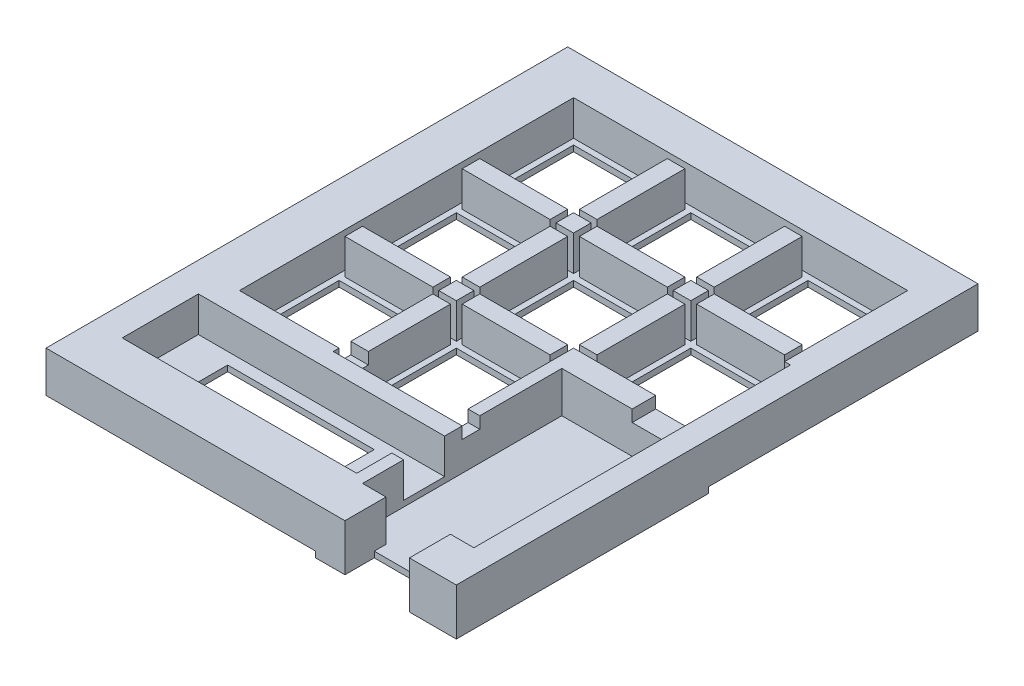
SolidWorks part; units mm, degrees
ref_plane "前视基准面" through (0, 0, 0) normal (0, 0, 1) x (1, 0, 0)
ref_plane "上视基准面" through (0, 0, 0) normal (0, 1, 0) x (1, 0, 0)
ref_plane "右视基准面" through (0, 0, 0) normal (1, 0, 0) x (0, 0, -1)
sketch "草图1" plane through (0, 0, 0) normal (0, 1, 0) x (1, 0, 0)
  line L1 (0, 0) -> (71, 0)
  line L2 (0, 0) -> (0, 67)
  line L3 (0, 67) -> (71, 67)
  line L4 (71, 0) -> (71, 67)
  dimension "D1" = 71
  dimension "D2" = 67
extrude "凸台-拉伸2" add sketch "草图1" along normal blind 5
extrude "凸台-拉伸3" add sketch "草图1<2>" along normal blind 7
sketch "草图1<2>" plane through (0, 0, 0) normal (0, 1, 0) x (1, 0, 0) same geometry as "草图1"
sketch "草图6" plane through (0, 0, 0) normal (0, 1, 0) x (1, 0, 0)
sketch "草图9" plane through (0, 0, 0) normal (0, 1, 0) x (1, 0, 0)
  line L0 (0, 0) -> (71, 0) construction
  line L1 (71, 0) -> (71, 67) construction
  line L3 (51, 0) -> (71, 0)
  line L4 (51, 0) -> (51, 20)
  line L5 (51, 20) -> (71, 20)
  line L6 (71, 0) -> (71, 20)
  point P0 (51, 0)
  point P1 (71, 20)
  dimension "D1" = 20
  dimension "D2" = 20
extrude "切除-拉伸5" cut sketch "草图9" along normal blind 36
sketch "草图10" plane through (0, 0, 0) normal (0, 1, 0) x (1, 0, 0)
  line L0 (71, 20) -> (71, 67) construction
  line L1 (0, 67) -> (0, 0) construction
  line L2 (71, 67) -> (0, 67) construction
  line L3 (10, 60) -> (10, 45)
  line L4 (10, 45) -> (25, 45)
  line L5 (25, 45) -> (25, 60)
  line L6 (25, 60) -> (10, 60)
  line L7 (30, 45) -> (30, 60)
  line L8 (30, 60) -> (45, 60)
  line L9 (45, 60) -> (45, 45)
  line L10 (45, 45) -> (30, 45)
  line L11 (50, 45) -> (50, 60)
  line L12 (50, 60) -> (65, 60)
  line L13 (65, 60) -> (65, 45)
  line L14 (65, 45) -> (50, 45)
  line L15 (50, 25) -> (50, 40)
  line L16 (50, 40) -> (65, 40)
  line L17 (65, 40) -> (65, 25)
  line L18 (65, 25) -> (50, 25)
  line L19 (0, 0) -> (51, 0) construction
  line L20 (30, 25) -> (45, 25)
  line L21 (30, 25) -> (30, 40)
  line L22 (30, 40) -> (45, 40)
  line L23 (45, 25) -> (45, 40)
  line L24 (10, 25) -> (25, 25)
  line L25 (10, 25) -> (10, 40)
  line L26 (10, 40) -> (25, 40)
  line L27 (25, 25) -> (25, 40)
  line L28 (10, 5) -> (25, 5)
  line L29 (10, 5) -> (10, 20)
  line L30 (10, 20) -> (25, 20)
  line L31 (25, 5) -> (25, 20)
  line L32 (30, 5) -> (45, 5)
  line L33 (30, 5) -> (30, 20)
  line L34 (30, 20) -> (45, 20)
  line L35 (45, 5) -> (45, 20)
  line L36 (50, 0) -> (51, 0)
  line L37 (50, 0) -> (50, 20)
  line L38 (50, 20) -> (51, 20)
  line L39 (51, 0) -> (51, 20)
  line L40 (51, 20) -> (51, 0) construction
  point P0 (71, 60)
  point P1 (71, 45)
  point P5 (71, 40)
  point P6 (71, 25)
  point P7 (0, 5)
  point P8 (0, 0)
  point P11 (0, 5)
  point P13 (0, 20)
  point P14 (0, 20)
  point P15 (0, 5)
  point P16 (65, 67)
  point P17 (50, 67)
  point P20 (45, 67)
  point P21 (30, 67)
  point P22 (25, 67)
  point P23 (10, 67)
  point P64 (66, 67)
  point P65 (49, 67)
  point P66 (45.5452, 67)
  dimension "D1" = 7
  dimension "D2" = 15
  dimension "D3" = 5
  dimension "D4" = 15
  dimension "D5" = 5
  dimension "D6" = 15
  dimension "D7" = 6
  dimension "D8" = 15
  dimension "D9" = 5
  dimension "D10" = 15
  dimension "D11" = 5
  dimension "D12" = 15
  dimension "D13" = 1
  dimension "D14" = 1
extrude "切除-拉伸6" cut sketch "草图10" along normal blind 32
ref_plane "上中" through (0, 1, 0) normal (0, 1, 0) x (1, 0, 0)
sketch "草图14" plane through (0, 1, 0) normal (0, 1, 0) x (1, 0, 0)
  line L0 (0, 67) -> (0, 0) construction
  line L5 (71, 67) -> (0, 67) construction
  line L6 (71, 20) -> (71, 67) construction
  line L7 (66, 24) -> (65, 24)
  line L12 (50, 61) -> (49, 61)
  line L13 (50, 61) -> (50, 24)
  line L14 (50, 24) -> (49, 24)
  line L15 (49, 61) -> (49, 24)
  line L16 (66, 24) -> (66, 61)
  line L17 (66, 61) -> (65, 61)
  line L18 (65, 24) -> (65, 61)
  line L32 (30, 61) -> (29, 61)
  line L33 (30, 61) -> (30, 4)
  line L34 (30, 4) -> (29, 4)
  line L35 (29, 61) -> (29, 4)
  line L36 (25, 4) -> (26, 4)
  line L37 (25, 4) -> (25, 61)
  line L38 (25, 61) -> (26, 61)
  line L39 (26, 4) -> (26, 61)
  line L40 (9, 4) -> (10, 4)
  line L41 (9, 4) -> (9, 61)
  line L42 (9, 61) -> (10, 61)
  line L43 (10, 4) -> (10, 61)
  line L44 (46, 4) -> (45, 4)
  line L45 (46, 4) -> (46, 61)
  line L46 (46, 61) -> (45, 61)
  line L47 (45, 4) -> (45, 61)
  point P0 (66, 67)
  point P1 (65, 67)
  point P4 (71, 24)
  point P5 (71, 61)
  point P12 (50, 67)
  point P15 (49, 67)
  point P16 (46, 67)
  point P21 (45, 67)
  point P26 (30, 67)
  point P27 (29, 67)
  point P28 (26, 67)
  point P29 (25, 67)
  point P34 (10, 67)
  point P35 (9, 67)
  point P40 (0, 5)
  point P41 (0, 4)
  dimension "D1" = 5
  dimension "D2" = 1
  dimension "D3" = 4
  dimension "D4" = 6
  dimension "D5" = 21
  dimension "D6" = 1
  dimension "D7" = 3
  dimension "D8" = 1
  dimension "D9" = 15
  dimension "D10" = 1
  dimension "D11" = 3
  dimension "D12" = 1
  dimension "D13" = 15
  dimension "D14" = 1
  dimension "D15" = 5
  dimension "D16" = 1
extrude "切除-拉伸7" cut sketch "草图14" along normal blind 19
sketch "草图15" plane through (0, 1, 0) normal (0, 1, 0) x (1, 0, 0)
  line L0 (0, 67) -> (0, 0) construction
  line L1 (71, 67) -> (0, 67) construction
  line L3 (9, 4) -> (46, 4)
  line L4 (9, 4) -> (9, 5)
  line L5 (9, 5) -> (46, 5)
  line L6 (46, 4) -> (46, 5)
  line L7 (9, 25) -> (66, 25)
  line L8 (9, 25) -> (9, 24)
  line L9 (9, 24) -> (66, 24)
  line L10 (66, 25) -> (66, 24)
  line L11 (9, 45) -> (66, 45)
  line L12 (9, 45) -> (9, 44)
  line L13 (9, 44) -> (66, 44)
  line L14 (66, 45) -> (66, 44)
  line L15 (9, 20) -> (46, 20)
  line L16 (9, 20) -> (9, 21)
  line L17 (9, 21) -> (46, 21)
  line L18 (46, 20) -> (46, 21)
  line L19 (9, 40) -> (66, 40)
  line L20 (9, 40) -> (9, 41)
  line L21 (9, 41) -> (66, 41)
  line L22 (66, 40) -> (66, 41)
  line L23 (9, 60) -> (66, 60)
  line L24 (9, 60) -> (9, 61)
  line L25 (9, 61) -> (66, 61)
  line L26 (66, 60) -> (66, 61)
  point P0 (0, 4)
  point P1 (0, 5)
  point P5 (0, 20)
  point P6 (0, 21)
  point P7 (0, 24)
  point P8 (0, 25)
  point P9 (0, 40)
  point P10 (0, 41)
  point P11 (0, 44)
  point P12 (0, 45)
  point P13 (0, 60)
  point P14 (0, 61)
  point P15 (66, 67)
  point P16 (49, 67)
  point P20 (9, 67)
  point P21 (46, 67)
  dimension "D1" = 4
  dimension "D2" = 1
  dimension "D3" = 15
  dimension "D4" = 1
  dimension "D5" = 3
  dimension "D6" = 1
  dimension "D7" = 15
  dimension "D8" = 1
  dimension "D9" = 3
  dimension "D10" = 1
  dimension "D11" = 15
  dimension "D12" = 1
  dimension "D13" = 5
  dimension "D14" = 22
  dimension "D15" = 62
  dimension "D16" = 25
extrude "切除-拉伸8" cut sketch "草图15" along normal blind 27
sketch "草图16" plane through (0, 0, 0) normal (0, 1, 0) x (1, 0, 0)
  line L0 (0, 0) -> (50, 0) construction
  line L1 (71, 20) -> (71, 67) construction
  line L3 (48, 0) -> (71, 0)
  line L4 (48, 0) -> (48, 21)
  line L5 (48, 21) -> (71, 21)
  line L6 (71, 0) -> (71, 21)
  point P0 (48, 0)
  point P1 (71, 21)
  dimension "D1" = 2
  dimension "D2" = 1
extrude "切除-拉伸9" cut sketch "草图16" along normal blind 17
sketch "草图17" plane through (0, 0, 0) normal (0, 1, 0) x (1, 0, 0)
  line L0 (71, 67) -> (0, 67) construction
  line L2 (1, 67) -> (0, 67)
  line L3 (1, 67) -> (1, 0)
  line L4 (1, 0) -> (0, 0)
  line L5 (0, 67) -> (0, 0)
  point P0 (1, 67)
  point P1 (1, 67)
  point P4 (0, 67)
  dimension "D1" = 1
extrude "切除-拉伸10" cut sketch "草图17" along normal blind 27
ref_plane "上下" through (0, 7, 0) normal (0, 1, 0) x (1, 0, 0)
sketch "草图18" plane through (0, 7, 0) normal (0, 1, 0) x (1, 0, 0)
  line L0 (66, 24) -> (66, 61) construction
  line L1 (66, 40) -> (67, 40)
  line L2 (66, 40) -> (66, 21)
  line L3 (66, 21) -> (67, 21)
  line L4 (67, 40) -> (67, 21)
  line L5 (71, 21) -> (48, 21) construction
extrude "切除-拉伸11" cut sketch "草图18" against normal blind 1
sketch "草图19" plane through (0, 7, 0) normal (0, 1, 0) x (1, 0, 0)
  line L1 (65, 40) -> (67, 40)
  line L2 (65, 40) -> (65, 21)
  line L3 (65, 21) -> (67, 21)
  line L4 (67, 40) -> (67, 21)
extrude "切除-拉伸12" cut sketch "草图19" against normal blind 1
sketch "草图20" plane through (0, 7, 0) normal (0, 1, 0) x (1, 0, 0)
  line L0 (65, 21) -> (48, 21) construction
  line L1 (46, 24) -> (66, 24) construction
  line L2 (63, 21) -> (64, 21)
  line L3 (63, 21) -> (63, 24)
  line L4 (63, 24) -> (64, 24)
  line L5 (64, 21) -> (64, 24)
  point P0 (64, 21)
  point P1 (63, 21)
  dimension "D1" = 1
  dimension "D2" = 1
extrude "切除-拉伸13" cut sketch "草图20" against normal blind 1
sketch "草图21" plane through (0, 7, 0) normal (0, 1, 0) x (1, 0, 0)
  line L0 (46, 4) -> (46, 24) construction
  line L1 (48, 21) -> (48, 0) construction
  line L2 (46, 5) -> (48, 5)
  line L3 (46, 5) -> (46, 6)
  line L4 (46, 6) -> (48, 6)
  line L5 (48, 5) -> (48, 6)
  point P0 (46, 6)
  dimension "D1" = 2
extrude "切除-拉伸15" cut sketch "草图21" against normal blind 1
sketch "草图22" plane through (0, 7, 0) normal (0, 1, 0) x (1, 0, 0)
  line L0 (48, 21) -> (48, 6) construction
  line L2 (48, 20) -> (71, 20)
  line L3 (48, 20) -> (48, 21)
  line L4 (48, 21) -> (71, 21)
  line L5 (71, 20) -> (71, 21)
  point P0 (48, 20)
  dimension "D1" = 1
extrude "凸台-拉伸4" add sketch "草图22" against normal up to vertex (7 mm away) up to point (48, 0, -21)
sketch "草图23" plane through (0, 7, 0) normal (0, 1, 0) x (1, 0, 0)
  line L0 (48, 20) -> (71, 20) construction
  line L1 (63, 21) -> (64, 21)
  line L2 (63, 21) -> (63, 20)
  line L3 (63, 20) -> (64, 20)
  line L4 (64, 21) -> (64, 20)
  line L6 (65, 21) -> (67, 21)
  line L7 (65, 21) -> (65, 20)
  line L8 (65, 20) -> (67, 20)
  line L9 (67, 21) -> (67, 20)
extrude "切除-拉伸16" cut sketch "草图23" against normal blind 1
sketch "草图24" plane through (0, 7, 0) normal (0, 1, 0) x (1, 0, 0)
  line L1 (1, 67) -> (71, 67)
  line L2 (1, 67) -> (1, 68)
  line L3 (1, 68) -> (71, 68)
  line L4 (71, 67) -> (71, 68)
extrude "凸台-拉伸5" add sketch "草图24" against normal blind 7
sketch "草图27" plane through (0, 7, 0) normal (0, 1, 0) x (1, 0, 0)
  line L0 (1, 0) -> (48, 0) construction
  line L2 (6, 0) -> (1, 0)
  line L3 (6, 0) -> (6, -20)
  line L4 (6, -20) -> (1, -20)
  line L5 (1, 0) -> (1, -20)
  point P0 (6, 0)
  dimension "D1" = 5
extrude "凸台-拉伸6" add sketch "草图27" against normal blind 7
sketch "草图28" plane through (0, 7, 0) normal (0, 1, 0) x (1, 0, 0)
  line L0 (6, -20) -> (6, 0) construction
  line L2 (6, -20) -> (48, -20)
  line L3 (6, -20) -> (6, -12)
  line L4 (6, -12) -> (48, -12)
  line L5 (48, -20) -> (48, -12)
  point P0 (6, -12)
  dimension "D1" = 8
extrude "凸台-拉伸7" add sketch "草图28" against normal up to vertex (7 mm away) up to point (1, 0, -68)
sketch "草图29" plane through (0, 7, 0) normal (0, 1, 0) x (1, 0, 0)
  line L0 (48, -20) -> (48, -12) construction
  line L2 (48, -13) -> (6, -13)
  line L3 (48, -13) -> (48, -12)
  line L4 (48, -12) -> (6, -12)
  line L5 (6, -13) -> (6, -12)
  point P0 (48, -13)
  dimension "D1" = 1
extrude "切除-拉伸17" cut sketch "草图29" against normal blind 7
sketch "草图30" plane through (0, 7, 0) normal (0, 1, 0) x (1, 0, 0)
  line L1 (1, -20) -> (48, -20)
  line L2 (1, -20) -> (1, -21)
  line L3 (1, -21) -> (48, -21)
  line L4 (48, -20) -> (48, -21)
extrude "凸台-拉伸8" add sketch "草图30" against normal blind 7
sketch "草图31" plane through (0, 7, 0) normal (0, 1, 0) x (1, 0, 0)
  line L0 (6, -13) -> (48, -13) construction
  line L2 (48, -13) -> (46, -13)
  line L3 (48, -13) -> (48, -10)
  line L4 (48, -10) -> (46, -10)
  line L5 (46, -13) -> (46, -10)
  point P0 (46, -13)
  dimension "D1" = 2
extrude "凸台-拉伸9" add sketch "草图31" against normal blind 7
sketch "草图32" plane through (0, 7, 0) normal (0, 1, 0) x (1, 0, 0)
  line L1 (71, 20) -> (67, 20)
  line L2 (71, 20) -> (71, -21)
  line L3 (71, -21) -> (67, -21)
  line L4 (67, 20) -> (67, -21)
extrude "凸台-拉伸11" add sketch "草图32" against normal blind 7
sketch "草图33" plane through (0, 7, 0) normal (0, 1, 0) x (1, 0, 0)
  line L0 (67, -21) -> (67, 40) construction
  line L2 (67, -21) -> (63, -21)
  line L3 (67, -21) -> (67, -17)
  line L4 (67, -17) -> (63, -17)
  line L5 (63, -21) -> (63, -17)
  point P0 (67, -17)
  dimension "D1" = 4
extrude "凸台-拉伸12" add sketch "草图33" against normal blind 7
sketch "草图34" plane through (0, 7, 0) normal (0, 1, 0) x (1, 0, 0)
  line L0 (48, -21) -> (48, -10) construction
  line L2 (48, -17) -> (52, -17)
  line L3 (48, -17) -> (48, -21)
  line L4 (48, -21) -> (52, -21)
  line L5 (52, -17) -> (52, -21)
  point P0 (48, -17)
  dimension "D1" = 4
extrude "凸台-拉伸13" add sketch "草图34" against normal blind 7
sketch "草图35" plane through (0, 7, 0) normal (0, 1, 0) x (1, 0, 0)
  line L0 (52, -21) -> (52, -17) construction
  line L3 (67, 20) -> (67, -17) construction
  line L4 (48, -17) -> (48, -10) construction
  line L5 (67, -17) -> (48, -17)
  line L6 (67, -17) -> (67, -14)
  line L7 (67, -14) -> (48, -14)
  line L8 (48, -17) -> (48, -14)
  point P0 (52, -19)
  point P6 (67, -14)
  dimension "D1" = 3
extrude "凸台-拉伸14" add sketch "草图35" against normal blind 7
sketch "草图36" plane through (0, 0, 0) normal (0, 1, 0) x (1, 0, 0)
  line L0 (67, -14) -> (48, -14) construction
  line L1 (52, -17) -> (63, -17)
  line L2 (52, -17) -> (52, -14)
  line L3 (52, -14) -> (63, -14)
  line L4 (63, -17) -> (63, -14)
extrude "切除-拉伸20" cut sketch "草图36" along normal blind 7
sketch "草图37" plane through (0, 7, 0) normal (0, 1, 0) x (1, 0, 0)
  line L0 (1, -21) -> (52, -21) construction
  line L1 (1, -21) -> (1, 68) construction
  line L2 (63, -21) -> (71, -21) construction
  line L3 (71, -21) -> (71, 68) construction
  line L4 (71, 68) -> (1, 68) construction
  circle A0 centre (3, -18) radius 0.5
  circle A1 centre (69.5, -18) radius 0.5
  circle A2 centre (69.5, 64) radius 0.5
  circle A3 centre (3.5, 64) radius 0.5
  point P0 (3, -21)
  point P1 (1, -18)
  point P9 (69.5, -21)
  point P10 (71, -18)
  point P18 (69.5, 68)
  point P19 (71, 64)
  point P25 (3.5, 68)
  point P26 (1, 64)
  dimension "D3" = 1.5
  dimension "D5" = 1.5
  dimension "D7" = 2.5
  dimension "D1" = 2
  dimension "D2" = 3
  dimension "D4" = 3
  dimension "D6" = 4
  dimension "D8" = 4
extrude "切除-拉伸22" cut sketch "草图37" against normal blind 9
sketch "草图38" plane through (0, 0, 0) normal (0, 1, 0) x (1, 0, 0)
  circle A0 centre (69.5, -18) radius 1
  circle A1 centre (69.5, 64) radius 1
  circle A2 centre (3.5, 64) radius 1
  circle A3 centre (3, -18) radius 1
extrude "切除-拉伸23" cut sketch "草图38" along normal blind 5
sketch "草图39" plane through (0, 7, 0) normal (0, 1, 0) x (1, 0, 0)
  line L0 (1, 68) -> (71, 68)
  line L1 (71, 68) -> (71, -21)
  line L2 (71, -21) -> (63, -21)
  line L3 (63, -21) -> (63, -14)
  line L4 (63, -14) -> (67, -14)
  line L5 (67, -14) -> (67, 40)
  line L6 (67, 40) -> (66, 40)
  line L7 (66, 40) -> (66, 61)
  line L8 (66, 61) -> (9, 61)
  line L9 (9, 61) -> (9, 4)
  line L10 (9, 4) -> (46, 4)
  line L11 (46, 4) -> (46, 5)
  line L12 (46, 5) -> (48, 5)
  line L13 (48, 5) -> (48, 0)
  line L14 (48, 0) -> (6, 0)
  line L15 (6, 0) -> (6, -13)
  line L16 (6, -13) -> (46, -13)
  line L17 (46, -13) -> (46, -10)
  line L18 (46, -10) -> (48, -10)
  line L19 (48, -10) -> (48, -14)
  line L20 (48, -14) -> (52, -14)
  line L21 (52, -14) -> (52, -21)
  line L22 (52, -21) -> (1, -21)
  line L23 (1, -21) -> (1, 68)
extrude "凸台-拉伸15" add sketch "草图39" along normal blind 1
extrude "切除-拉伸26" cut sketch "草图37<3>" against normal blind 12 and the other way blind 12
sketch "草图37<3>" plane through (0, 7, 0) normal (0, 1, 0) x (1, 0, 0) same geometry as "草图37"
sketch "草图40" plane through (0, 7, 0) normal (0, 1, 0) x (1, 0, 0)
  line L0 (46, 4) -> (46, 24) construction
  line L1 (46, 5) -> (48, 5)
  line L2 (46, 5) -> (46, 4)
  line L3 (46, 4) -> (48, 4)
  line L4 (48, 5) -> (48, 4)
  line L5 (46, 5) -> (46, 4) construction
  line L6 (48, 0) -> (48, 5) construction
extrude "切除-拉伸28" cut sketch "草图40" against normal blind 1 and the other way blind 9
sketch "草图42" plane through (0, 7, 0) normal (0, 1, 0) x (1, 0, 0)
  line L1 (48, 20) -> (63, 20) construction
  line L2 (65, 24) -> (62, 24) construction
  line L3 (65, 24) -> (65, 20) construction
  line L4 (65, 20) -> (62, 20) construction
  line L5 (62, 24) -> (62, 20) construction
  line L7 (62, 24) -> (65, 24)
  line L8 (62, 24) -> (62, 20)
  line L9 (62, 20) -> (65, 20)
  line L10 (65, 24) -> (65, 20)
extrude "切除-拉伸29" cut sketch "草图42" against normal blind 1
sketch "草图43" plane through (0, 7, 0) normal (0, 1, 0) x (1, 0, 0)
  line L0 (46, 6) -> (46, 24)
  line L1 (46, 24) -> (62, 24)
  line L2 (62, 24) -> (62, 20)
  line L3 (62, 20) -> (48, 20)
  line L4 (48, 20) -> (48, 6)
  line L5 (48, 6) -> (46, 6)
  line L6 (45, 44) -> (45, 41) construction
  line L7 (46, 40) -> (49, 40)
  line L8 (46, 40) -> (46, 25)
  line L9 (46, 25) -> (49, 25)
  line L10 (49, 40) -> (49, 25)
  line L11 (46, 60) -> (49, 60)
  line L12 (46, 60) -> (46, 45)
  line L13 (46, 45) -> (49, 45)
  line L14 (49, 60) -> (49, 45)
  line L15 (50, 44) -> (65, 44)
  line L16 (50, 44) -> (50, 41)
  line L17 (50, 41) -> (65, 41)
  line L18 (65, 44) -> (65, 41)
  line L19 (26, 60) -> (29, 60)
  line L20 (26, 60) -> (26, 45)
  line L21 (26, 45) -> (29, 45)
  line L22 (29, 60) -> (29, 45)
  line L23 (26, 40) -> (29, 40)
  line L24 (26, 40) -> (26, 25)
  line L25 (26, 25) -> (29, 25)
  line L26 (29, 40) -> (29, 25)
  line L27 (10, 44) -> (25, 44)
  line L28 (10, 44) -> (10, 41)
  line L29 (10, 41) -> (25, 41)
  line L30 (25, 44) -> (25, 41)
  line L31 (30, 44) -> (45, 44)
  line L32 (30, 44) -> (30, 41)
  line L33 (30, 41) -> (45, 41)
  line L34 (45, 44) -> (45, 41)
  line L35 (45, 41) -> (30, 41) construction
  line L37 (10, 24) -> (25, 24)
  line L38 (10, 24) -> (10, 21)
  line L39 (10, 21) -> (25, 21)
  line L40 (25, 24) -> (25, 21)
  line L41 (26, 20) -> (29, 20)
  line L42 (26, 20) -> (26, 5)
  line L43 (26, 5) -> (29, 5)
  line L44 (29, 20) -> (29, 5)
  line L45 (26, 24) -> (29, 24)
  line L46 (26, 24) -> (26, 21)
  line L47 (26, 21) -> (29, 21)
  line L48 (29, 24) -> (29, 21)
  line L49 (46, 44) -> (49, 44)
  line L50 (46, 44) -> (46, 41)
  line L51 (46, 41) -> (49, 41)
  line L52 (49, 44) -> (49, 41)
  line L53 (26, 44) -> (29, 44)
  line L54 (26, 44) -> (26, 41)
  line L55 (26, 41) -> (29, 41)
  line L56 (29, 44) -> (29, 41)
extrude "凸台-拉伸17" add sketch "草图43" along normal blind 1
sketch "草图44" plane through (0, 0, 0) normal (0, 1, 0) x (1, 0, 0)
  line L1 (46, -10) -> (48, -10)
  line L2 (46, -10) -> (46, -6.9982)
  line L3 (46, -6.9982) -> (48, -6.9982)
  line L4 (48, -10) -> (48, -6.9982)
extrude "凸台-拉伸18" add sketch "草图44" along normal blind 8
sketch "草图45" plane through (0, 1, 0) normal (0, 1, 0) x (1, 0, 0)
  line L0 (6, -13) -> (46, -13) construction
  line L1 (6, 0) -> (13, 0) construction
  line L2 (6, 0) -> (6, -13) construction
  line L3 (6, -13) -> (13, -13) construction
  line L4 (13, 0) -> (13, -13) construction
  line L6 (13, 0) -> (6, 0)
  line L7 (13, 0) -> (13, -13)
  line L8 (13, -13) -> (6, -13)
  line L9 (6, 0) -> (6, -13)
extrude "凸台-拉伸19" add sketch "草图45" along normal blind 1
sketch "草图46" plane through (0, 1, 0) normal (0, 1, 0) x (1, 0, 0)
  line L0 (6, -13) -> (46, -13) construction
  line L1 (48, 20) -> (48, 0) construction
  line L2 (38, -13) -> (48, -13)
  line L3 (38, -13) -> (38, 0)
  line L4 (38, 0) -> (48, 0)
  line L5 (48, -13) -> (48, 0)
  line L6 (6, 0) -> (48, 0) construction
  point P0 (38, -13)
  dimension "D1" = 32
extrude "凸台-拉伸20" add sketch "草图46" along normal blind 1
sketch "草图49" plane through (0, 0, 0) normal (0, 1, 0) x (1, 0, 0)
  line L1 (46, -14) -> (68.3792, -14)
  line L2 (46, -14) -> (46, 20.513)
  line L3 (46, 20.513) -> (68.3792, 20.513)
  line L4 (68.3792, -14) -> (68.3792, 20.513)
extrude "凸台-拉伸26" add sketch "草图49" along normal blind 1
sketch "草图50" plane through (0, 0, 0) normal (0, 1, 0) x (1, 0, 0)
  line L0 (71, 68) -> (1, 68) construction
  line L1 (5.3146, -15.8291) -> (1, -15.8291)
  line L2 (5.3146, -15.8291) -> (5.3146, -21)
  line L3 (5.3146, -21) -> (1, -21)
  line L4 (1, -15.8291) -> (1, -21)
  line L5 (66.8516, -15.8291) -> (71, -15.8291)
  line L6 (66.8516, -15.8291) -> (66.8516, -21)
  line L7 (66.8516, -21) -> (71, -21)
  line L8 (71, -15.8291) -> (71, -21)
  line L9 (66.8516, 61.6771) -> (71, 61.6771)
  line L10 (66.8516, 61.6771) -> (66.8516, 68)
  line L11 (66.8516, 68) -> (71, 68)
  line L12 (71, 61.6771) -> (71, 68)
  line L13 (71, -21) -> (71, 68) construction
  line L15 (6.8486, 61.6771) -> (1, 61.6771)
  line L16 (6.8486, 61.6771) -> (6.8486, 68)
  line L17 (6.8486, 68) -> (1, 68)
  line L18 (1, 61.6771) -> (1, 68)
extrude "凸台-拉伸27" add sketch "草图50" along normal blind 8
sketch "草图51" plane through (0, 1, 0) normal (0, 1, 0) x (1, 0, 0)
  line L1 (10, 5) -> (6, 5)
  line L2 (10, 5) -> (10, -13)
  line L3 (10, -13) -> (6, -13)
  line L4 (6, 5) -> (6, -13)
  line L5 (45, 5) -> (46, 5)
  line L6 (45, 5) -> (45, -13)
  line L7 (45, -13) -> (46, -13)
  line L8 (46, 5) -> (46, -13)
extrude "凸台-拉伸28" add sketch "草图51" against normal blind 1
sketch "草图52" plane through (0, 1, 0) normal (0, 1, 0) x (1, 0, 0)
  line L0 (63, -14) -> (63, -21) construction
  line L1 (52, -14) -> (63, -14) construction
  line L2 (52, -14) -> (52, -16) construction
  line L3 (52, -16) -> (63, -16) construction
  line L4 (63, -14) -> (63, -16) construction
  line L6 (52, -16) -> (63, -16)
  line L7 (52, -16) -> (52, -14)
  line L8 (52, -14) -> (63, -14)
  line L9 (63, -16) -> (63, -14)
extrude "凸台-拉伸29" add sketch "草图52" against normal blind 1
sketch "草图54" plane through (0, 1, 0) normal (0, 1, 0) x (1, 0, 0)
  line L0 (9, 61) -> (66, 61)
  line L1 (66, 61) -> (66, 24)
  line L2 (66, 24) -> (46, 24)
  line L3 (46, 24) -> (46, 4)
  line L4 (46, 4) -> (9, 4)
  line L5 (9, 4) -> (9, 61)
extrude "凸台-拉伸30" add sketch "草图54" along normal blind 1
sketch "草图55" plane through (0, 1, 0) normal (0, 1, 0) x (1, 0, 0)
  line L1 (65, 60) -> (50, 60)
  line L2 (65, 60) -> (65, 45)
  line L3 (65, 45) -> (50, 45)
  line L4 (50, 60) -> (50, 45)
  line L5 (45, 60) -> (30, 60)
  line L6 (45, 60) -> (45, 45)
  line L7 (45, 45) -> (30, 45)
  line L8 (30, 60) -> (30, 45)
  line L9 (25, 60) -> (10, 60)
  line L10 (25, 60) -> (25, 45)
  line L11 (25, 45) -> (10, 45)
  line L12 (10, 60) -> (10, 45)
  line L13 (65, 40) -> (50, 40)
  line L14 (65, 40) -> (65, 25)
  line L15 (65, 25) -> (50, 25)
  line L16 (50, 40) -> (50, 25)
  line L17 (45, 40) -> (30, 40)
  line L18 (45, 40) -> (45, 25)
  line L19 (45, 25) -> (30, 25)
  line L20 (30, 40) -> (30, 25)
  line L21 (25, 40) -> (10, 40)
  line L22 (25, 40) -> (25, 25)
  line L23 (25, 25) -> (10, 25)
  line L24 (10, 40) -> (10, 25)
  line L25 (45, 20) -> (30, 20)
  line L26 (45, 20) -> (45, 5)
  line L27 (45, 5) -> (30, 5)
  line L28 (30, 20) -> (30, 5)
  line L29 (25, 20) -> (10, 20)
  line L30 (25, 20) -> (25, 5)
  line L31 (25, 5) -> (10, 5)
  line L32 (10, 20) -> (10, 5)
extrude "切除-拉伸31" cut sketch "草图55" along normal blind 1
sketch "草图56" plane through (0, 1, 0) normal (0, 1, 0) x (1, 0, 0)
  line L0 (1, 68) -> (1, 2)
  line L1 (1, 68) -> (1, -21) construction
  line L2 (1, 2) -> (47, 2)
  line L3 (47, 2) -> (47, 22)
  line L4 (47, 22) -> (71, 22)
  line L5 (71, -21) -> (71, 68) construction
  line L6 (71, 22) -> (71, 68)
  line L7 (71, 68) -> (1, 68)
extrude "切除-拉伸32" cut sketch "草图56" against normal blind 1
sketch "草图57" plane through (0, 1, 0) normal (0, 1, 0) x (1, 0, 0)
  line L1 (47, 2) -> (1, 2)
  line L2 (47, 2) -> (47, -21)
  line L3 (47, -21) -> (1, -21)
  line L4 (1, 2) -> (1, -21)
extrude "切除-拉伸33" cut sketch "草图57" against normal blind 1
sketch "草图58" plane through (0, 7, 0) normal (0, 1, 0) x (1, 0, 0)
  line L1 (30, 21) -> (45, 21)
  line L2 (30, 21) -> (30, 24)
  line L3 (30, 24) -> (45, 24)
  line L4 (45, 21) -> (45, 24)
extrude "凸台-拉伸31" add sketch "草图58" along normal blind 1
sketch "草图59" plane through (0, 7, 0) normal (0, 1, 0) x (1, 0, 0)
  line L1 (48, 4) -> (26, 4)
  line L2 (48, 4) -> (48, 3)
  line L3 (48, 3) -> (26, 3)
  line L4 (26, 4) -> (26, 3)
extrude "切除-拉伸37" cut sketch "草图59" against normal blind 1 and the other way blind 2
sketch "草图60" plane through (0, 1, 0) normal (0, 1, 0) x (1, 0, 0)
  line L0 (38, 0) -> (38, -13) construction
  line L1 (13, 0) -> (38, 0)
  line L2 (13, 0) -> (13, -2)
  line L3 (13, -2) -> (38, -2)
  line L4 (38, 0) -> (38, -2)
  line L6 (13, -13) -> (38, -13)
  line L7 (13, -13) -> (13, -12)
  line L8 (13, -12) -> (38, -12)
  line L9 (38, -13) -> (38, -12)
extrude "凸台-拉伸32" add sketch "草图60" along normal blind 1
sketch "草图61" plane through (0, 7, 0) normal (0, 1, 0) x (1, 0, 0)
  line L0 (48, 20) -> (62, 20) construction
  line L1 (62, 24) -> (60, 24)
  line L2 (62, 24) -> (62, 20)
  line L3 (62, 20) -> (60, 20)
  line L4 (60, 24) -> (60, 20)
extrude "切除-拉伸39" cut sketch "草图61" against normal blind 1 and the other way blind 1
sketch "草图62" plane through (0, 7, 0) normal (0, 1, 0) x (1, 0, 0)
  line L0 (29, 5) -> (29, 20) construction
  line L1 (26, 5) -> (29, 5)
  line L2 (26, 5) -> (26, 6)
  line L3 (26, 6) -> (29, 6)
  line L4 (29, 5) -> (29, 6)
extrude "切除-拉伸40" cut sketch "草图62" against normal blind 1 and the other way blind 1
